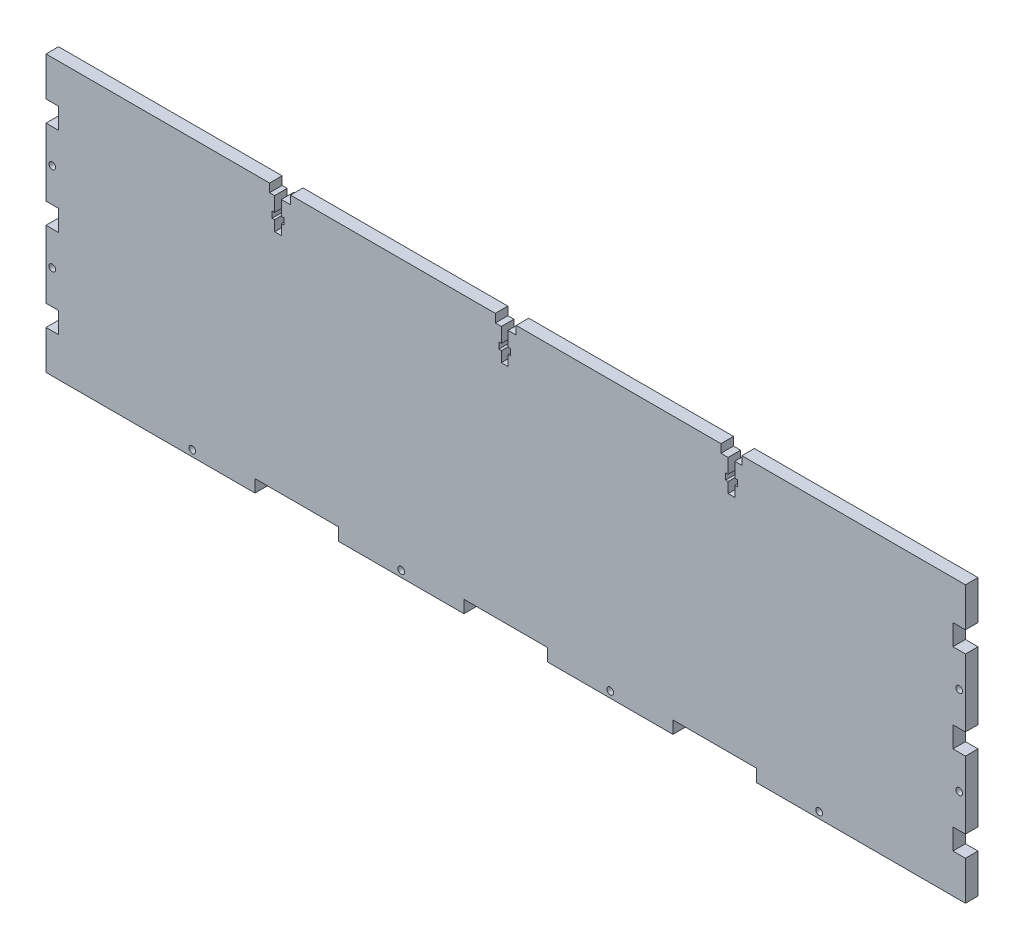
SolidWorks part; units mm, degrees
ref_plane "Front Plane" through (0, 0, 0) normal (0, 0, 1) x (1, 0, 0)
ref_plane "Top Plane" through (0, 0, 0) normal (0, 1, 0) x (1, 0, 0)
ref_plane "Right Plane" through (0, 0, 0) normal (1, 0, 0) x (0, 0, -1)
sketch "Sketch1" plane through (0, 0, 0) normal (0, 0, 1) x (1, 0, 0)
  line L1 (-220, -66) -> (220, -66)
  line L2 (-220, -66) -> (-220, 66)
  line L3 (-220, 66) -> (220, 66)
  line L4 (220, -66) -> (220, 66)
  line L5 (-220, -66) -> (220, 66) construction
  line L6 (-220, 66) -> (220, -66) construction
  point P0 (0, 0)
  dimension "D1" = 440
  dimension "D2" = 132
extrude "Boss-Extrude1" add sketch "Sketch1" along normal blind 6
sketch "Sketch2" plane through (0, 0, 0) normal (0, 0, -1) x (-1, 0, 0)
  line L0 (220, 47.3321) -> (220, 37.3321) construction
  line L1 (220, 37.3321) -> (214, 37.3321) construction
  line L2 (214, 37.3321) -> (214, 47.3321) construction
  line L3 (214, 47.3321) -> (220, 47.3321) construction
  line L12 (220, -37.3321) -> (220, -47.3321) construction
  line L13 (220, -47.3321) -> (214, -47.3321) construction
  line L14 (214, -47.3321) -> (214, -37.3321) construction
  line L15 (214, -37.3321) -> (220, -37.3321) construction
  line L16 (220, 47.3321) -> (220, 37.3321)
  line L17 (220, 37.3321) -> (214, 37.3321)
  line L18 (214, 37.3321) -> (214, 47.3321)
  line L19 (214, 47.3321) -> (220, 47.3321)
  line L20 (220, -37.3321) -> (220, -47.3321)
  line L21 (220, -47.3321) -> (214, -47.3321)
  line L22 (214, -47.3321) -> (214, -37.3321)
  line L23 (214, -37.3321) -> (220, -37.3321)
  line L24 (-214, -37.3321) -> (-214, -47.3321) construction
  line L25 (-214, -47.3321) -> (-220, -47.3321) construction
  line L26 (-220, -47.3321) -> (-220, -37.3321) construction
  line L27 (-220, -37.3321) -> (-214, -37.3321) construction
  line L28 (-214, 47.3321) -> (-214, 37.3321) construction
  line L29 (-214, 37.3321) -> (-220, 37.3321) construction
  line L30 (-220, 37.3321) -> (-220, 47.3321) construction
  line L31 (-220, 47.3321) -> (-214, 47.3321) construction
  line L32 (-214, -37.3321) -> (-214, -47.3321)
  line L33 (-214, -47.3321) -> (-220, -47.3321)
  line L34 (-220, -47.3321) -> (-220, -37.3321)
  line L35 (-220, -37.3321) -> (-214, -37.3321)
  line L36 (-214, 47.3321) -> (-214, 37.3321)
  line L37 (-214, 37.3321) -> (-220, 37.3321)
  line L38 (-220, 37.3321) -> (-220, 47.3321)
  line L39 (-220, 47.3321) -> (-214, 47.3321)
  line L44 (220, -5) -> (220, 5)
  line L45 (214, -5) -> (220, -5)
  line L46 (214, 5) -> (214, -5)
  line L47 (220, 5) -> (214, 5)
  line L48 (220, -5) -> (220, 5)
  line L49 (214, -5) -> (220, -5)
  line L50 (214, 5) -> (214, -5)
  line L51 (220, 5) -> (214, 5)
  line L52 (-214, -5) -> (-214, 5)
  line L53 (-220, -5) -> (-214, -5)
  line L54 (-220, 5) -> (-220, -5)
  line L55 (-214, 5) -> (-220, 5)
  line L56 (-214, -5) -> (-214, 5)
  line L57 (-220, -5) -> (-214, -5)
  line L58 (-220, 5) -> (-220, -5)
  line L59 (-214, 5) -> (-220, 5)
  circle A0 centre (217, 21.1661) radius 1.6 construction
  circle A1 centre (217, -21.1661) radius 1.6 construction
  circle A2 centre (-217, 21.1661) radius 1.6 construction
  circle A3 centre (-217, -21.1661) radius 1.6 construction
  circle A4 centre (217, 21.1661) radius 1.6
  circle A5 centre (217, -21.1661) radius 1.6
  circle A6 centre (-217, 21.1661) radius 1.6
  circle A7 centre (-217, -21.1661) radius 1.6
  dimension "D2" = 0
  dimension "D3" = 0
extrude "Cut-Extrude1" cut sketch "Sketch2" against normal up to next
sketch "Sketch3" plane through (0, 0, 0) normal (0, 0, -1) x (-1, 0, 0)
  circle A0 centre (-150, -63) radius 1.6 construction
  circle A1 centre (-50, -63) radius 1.6 construction
  circle A2 centre (50, -63) radius 1.6 construction
  circle A3 centre (150, -63) radius 1.6 construction
  circle A4 centre (-150, -63) radius 1.6
  circle A5 centre (-50, -63) radius 1.6
  circle A6 centre (50, -63) radius 1.6
  circle A7 centre (150, -63) radius 1.6
extrude "Cut-Extrude2" cut sketch "Sketch3" against normal up to next
sketch "Sketch4" plane through (0, 0, 0) normal (0, 0, -1) x (-1, 0, 0)
  line L0 (80, -66) -> (120, -66) construction
  line L1 (120, -66) -> (120, -60) construction
  line L2 (120, -60) -> (80, -60) construction
  line L3 (80, -60) -> (80, -66) construction
  line L4 (-20, -66) -> (20, -66) construction
  line L5 (20, -66) -> (20, -60) construction
  line L6 (20, -60) -> (-20, -60) construction
  line L7 (-20, -60) -> (-20, -66) construction
  line L8 (-120, -66) -> (-80, -66) construction
  line L9 (-80, -66) -> (-80, -60) construction
  line L10 (-80, -60) -> (-120, -60) construction
  line L11 (-120, -60) -> (-120, -66) construction
  line L12 (80, -66) -> (120, -66)
  line L13 (120, -66) -> (120, -60)
  line L14 (120, -60) -> (80, -60)
  line L15 (80, -60) -> (80, -66)
  line L16 (-20, -66) -> (20, -66)
  line L17 (20, -66) -> (20, -60)
  line L18 (20, -60) -> (-20, -60)
  line L19 (-20, -60) -> (-20, -66)
  line L20 (-120, -66) -> (-80, -66)
  line L21 (-80, -66) -> (-80, -60)
  line L22 (-80, -60) -> (-120, -60)
  line L23 (-120, -60) -> (-120, -66)
extrude "Cut-Extrude3" cut sketch "Sketch4" against normal up to next
sketch "Sketch5" plane through (0, 66, 0) normal (0, 1, 0) x (1, 0, 0)
  line L0 (220, 0) -> (-220, 0) construction
  line L1 (-113, -6) -> (-103, -6)
  line L2 (-113, -6) -> (-113, 0)
  line L3 (-113, 0) -> (-103, 0)
  line L4 (-103, -6) -> (-103, 0)
  line L5 (-113, -6) -> (-103, 0) construction
  line L6 (-113, 0) -> (-103, -6) construction
  line L7 (-103, -6) -> (-103, 0) construction
  line L8 (5, -6) -> (5, 0) construction
  line L9 (-5, -6) -> (5, -6)
  line L10 (-5, -6) -> (-5, 0)
  line L11 (-5, 0) -> (5, 0)
  line L12 (5, -6) -> (5, 0)
  line L13 (-5, -6) -> (5, 0) construction
  line L14 (-5, 0) -> (5, -6) construction
  line L15 (113, -6) -> (113, 0) construction
  line L16 (103, -6) -> (113, -6)
  line L17 (103, -6) -> (103, 0)
  line L18 (103, 0) -> (113, 0)
  line L19 (113, -6) -> (113, 0)
  line L20 (103, -6) -> (113, 0) construction
  line L21 (103, 0) -> (113, -6) construction
  point P0 (-108, -3)
  point P10 (0, -3)
  point P18 (108, -3)
extrude "Cut-Extrude4" cut sketch "Sketch5" against normal blind 4
sketch "Sketch6" plane through (0, 0, 0) normal (0, 0, -1) x (-1, 0, 0)
  line L0 (-108, 62) -> (-108, 47) construction
  line L1 (-113, 62) -> (-103, 62) construction
  line L2 (-109.6, 62) -> (-109.6, 55)
  line L3 (-106.4, 62) -> (-106.4, 55)
  line L4 (-109.6, 62) -> (-106.4, 62)
  line L5 (-109.6, 47) -> (-106.4, 47)
  line L6 (-106.4, 52) -> (-105.2, 52)
  line L7 (-110.8, 55) -> (-109.6, 55)
  line L8 (-110.8, 55) -> (-110.8, 52)
  line L9 (-110.8, 52) -> (-109.6, 52)
  line L10 (-105.2, 55) -> (-105.2, 52)
  line L11 (-110.8, 55) -> (-105.2, 52) construction
  line L12 (-110.8, 52) -> (-105.2, 55) construction
  line L13 (-106.4, 52) -> (-106.4, 47)
  line L14 (-106.4, 62) -> (-106.4, 47) construction
  line L15 (-109.6, 52) -> (-109.6, 47)
  line L16 (-109.6, 62) -> (-109.6, 47) construction
  line L17 (-106.4, 55) -> (-105.2, 55)
  line L18 (-1.1, 62) -> (-1.1, 55)
  line L19 (2.1, 62) -> (2.1, 55)
  line L20 (-1.1, 62) -> (2.1, 62)
  line L21 (-1.1, 47) -> (2.1, 47)
  line L22 (2.1, 52) -> (3.3, 52)
  line L23 (-2.3, 55) -> (-1.1, 55)
  line L24 (-2.3, 55) -> (-2.3, 52)
  line L25 (-2.3, 52) -> (-1.1, 52)
  line L26 (3.3, 55) -> (3.3, 52)
  line L27 (2.1, 52) -> (2.1, 47)
  line L28 (-1.1, 52) -> (-1.1, 47)
  line L29 (2.1, 55) -> (3.3, 55)
  line L30 (0.5, 62) -> (0.5, 47) construction
  line L31 (-2.3, 55) -> (3.3, 52) construction
  line L32 (-2.3, 52) -> (3.3, 55) construction
  line L33 (107.4, 62) -> (107.4, 55)
  line L34 (110.6, 62) -> (110.6, 55)
  line L35 (107.4, 62) -> (110.6, 62)
  line L36 (107.4, 47) -> (110.6, 47)
  line L37 (110.6, 52) -> (111.8, 52)
  line L38 (106.2, 55) -> (107.4, 55)
  line L39 (106.2, 55) -> (106.2, 52)
  line L40 (106.2, 52) -> (107.4, 52)
  line L41 (111.8, 55) -> (111.8, 52)
  line L42 (110.6, 52) -> (110.6, 47)
  line L43 (107.4, 52) -> (107.4, 47)
  line L44 (110.6, 55) -> (111.8, 55)
  line L45 (109, 62) -> (109, 47) construction
  line L46 (106.2, 55) -> (111.8, 52) construction
  line L47 (106.2, 52) -> (111.8, 55) construction
  point P8 (-108, 53.5)
  point P25 (0.5, 53.5)
  point P40 (109, 53.5)
  dimension "D1" = 15
  dimension "D4" = 5.6
  dimension "D5" = 3
  dimension "D6" = 7
  dimension "D2" = 1.6
  dimension "D3" = 1.6
  dimension "D7" = 3
extrude "Cut-Extrude5" cut sketch "Sketch6" against normal up to next
equation "\"m3_depth\"=15"
equation "\"D1@Sketch6\"=\"m3_depth\""
equation "\"m3_nut_width\"=5.6"
equation "\"D4@Sketch6\"=\"m3_nut_width\""
equation "\"m3_nut_thickness\"=3"
equation "\"D5@Sketch6\"=\"m3_nut_thickness\""
equation "\"m3_nut_depth\"=7"
equation "\"D6@Sketch6\"=\"m3_nut_depth\""
